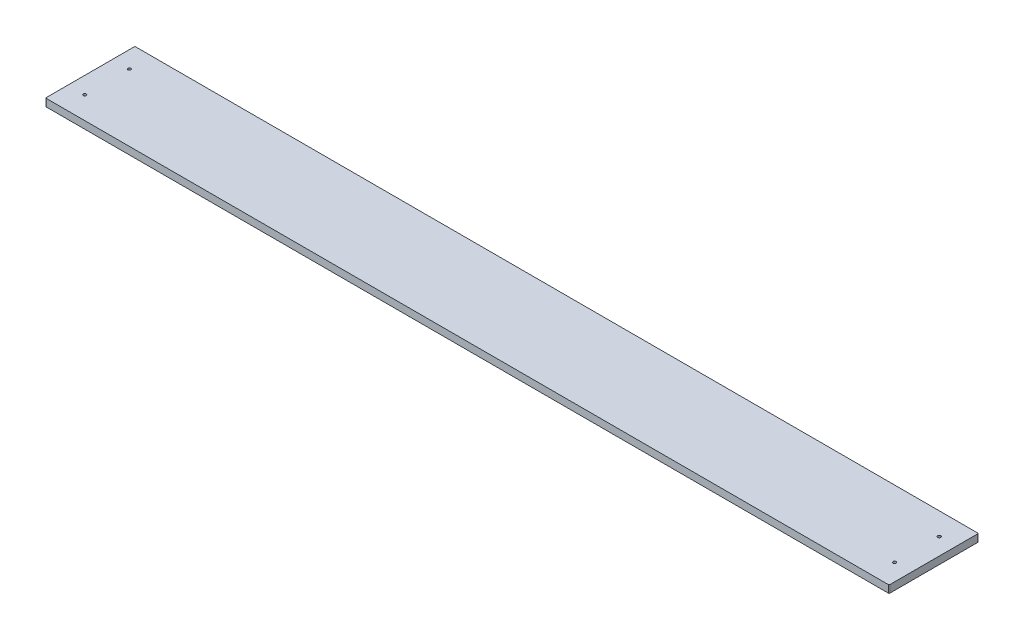
SolidWorks part; units mm, degrees
ref_plane "Front Plane" through (0, 0, 0) normal (0, 0, 1) x (1, 0, 0)
ref_plane "Top Plane" through (0, 0, 0) normal (0, 1, 0) x (1, 0, 0)
ref_plane "Right Plane" through (0, 0, 0) normal (1, 0, 0) x (0, 0, -1)
sketch "Sketch1" plane through (0, 0, 0) normal (0, 1, 0) x (1, 0, 0)
  line L1 (-719.5344, -76.2) -> (719.5344, -76.2)
  line L2 (-719.5344, -76.2) -> (-719.5344, 76.2)
  line L3 (-719.5344, 76.2) -> (719.5344, 76.2)
  line L4 (719.5344, -76.2) -> (719.5344, 76.2)
  line L5 (-719.5344, -76.2) -> (719.5344, 76.2) construction
  line L6 (-719.5344, 76.2) -> (719.5344, -76.2) construction
  point P0 (0, 0)
  dimension "D1" = 1439.0687
  dimension "D2" = 152.4
extrude "Boss-Extrude1" add sketch "Sketch1" along normal blind 12.7
sketch "Sketch2" plane through (0, 12.7, 0) normal (0, 1, 0) x (1, 0, 0)
  line L0 (-610.2712, -25.4) -> (-178.4498, -25.4) construction
  line L1 (-719.5344, -76.2) -> (719.5344, -76.2) construction
  text T0 "OpenAg" font "Circular Std Bold" height in points 190
  point P5 (0, 0)
  point P6 (0, 0)
  dimension "D1" = 50.8
extrude "Cut-Extrude1" [suppressed] cut sketch "Sketch2" against normal through all
sketch "Sketch4" [suppressed] plane through (0, 12.7, 0) normal (0, 1, 0) x (1, 0, 0)
  line L0 (-481.0791, -2.1861) -> (-481.0791, -9.1196) construction
  line L1 (-472.6906, -2.1889) -> (-489.4677, -2.1833) construction
  line L2 (-489.6966, -9.1213) -> (-463.0424, -9.1158) construction
  line L3 (-579.6316, -16.9796) -> (-579.6316, -26.7667) construction
  line L4 (-482.6666, -9.1196) -> (-479.4916, -9.1196)
  line L5 (-482.6666, -9.1196) -> (-482.6666, -2.1861)
  line L6 (-482.6666, -2.1861) -> (-479.4916, -2.1861)
  line L7 (-479.4916, -9.1196) -> (-479.4916, -2.1861)
  line L8 (-482.6666, -9.1196) -> (-479.4916, -2.1861) construction
  line L9 (-482.6666, -2.1861) -> (-479.4916, -9.1196) construction
  line L10 (-388.2394, -3.6437) -> (-388.2394, -13.2985) construction
  line L11 (-525.1122, -25.8875) -> (-525.1122, -16.9456)
  line L12 (-380.7736, -3.6437) -> (-395.7052, -3.6437) construction
  line L13 (-521.9372, -26.0295) -> (-521.9372, -16.7138)
  line L14 (-524.0627, -25.9896) -> (-522.7776, -16.8731) construction
  line L15 (-524.2553, -16.9905) -> (-522.9785, -26.048) construction
  line L16 (-581.2191, -26.7131) -> (-581.2191, -16.9176)
  line L18 (-578.0441, -26.7134) -> (-578.0441, -16.9192)
  line L19 (-580.3862, -26.7446) -> (-578.7706, -16.9569) construction
  line L20 (-580.4927, -16.9565) -> (-578.8769, -26.7447) construction
  line L21 (-389.8269, -3.6437) -> (-386.6519, -3.6437)
  line L22 (-389.8269, -13.2985) -> (-389.8269, -3.6437)
  line L24 (-386.6519, -13.2985) -> (-386.6519, -3.6437)
  line L25 (-388.9668, -13.2985) -> (-387.2862, -3.6437) construction
  line L26 (-389.1926, -3.6437) -> (-387.5119, -13.2985) construction
  line L27 (-389.8269, -13.2985) -> (-386.6519, -13.2985)
  line L28 (-399.2095, -13.2985) -> (-377.2693, -13.2985) construction
  line L29 (-340.3453, -23.877) -> (-340.3453, -14.833)
  line L31 (-337.1703, -23.518) -> (-337.1703, -14.7794)
  line L32 (-339.557, -23.8374) -> (-337.9312, -14.8845) construction
  line L33 (-339.5803, -14.9074) -> (-337.9888, -23.6712) construction
  spline S0 degree 3 poles (-232.3826, -4014.5128) (-589.5598, 58.6836) (-550.0161, -30.9294) (-518.8976, -25.6707) (-517.1471, -25.2295) (-515.5068, -24.6023) (-513.9595, -23.8362) (-512.5345, -22.874) (-511.2004, -21.767) (-509.9827, -20.4984) (-508.8843, -19.1019) (-507.9211, -17.6011) (-507.1154, -15.9982) (-506.4387, -14.3072) (-505.9115, -12.5134) (-505.5254, -10.6262) (-501.1651, 26.981) (-579.9114, 69.01) (3491.1558, -142.4925) knots -3.037277 -3.037277 -3.037277 -3.037277 0.066422 0.130142 0.191626 0.251229 0.309849 0.368247 0.427084 0.487286 0.548172 0.608983 0.669794 0.731835 0.795476 0.861221 0.929106 4.671597 4.671597 4.671597 4.671597 only from (-522.6618, -26.0613) to (-505.2258, -6.5974) construction
  spline S1 degree 3 poles (-3524.9039, -2675.861) (-493.7914, 65.5371) (-547.0805, -9.9244) (-531.7012, -23.3014) (-530.5727, -24.0724) (-529.2816, -24.7561) (-527.8328, -25.3165) (-526.2372, -25.7369) (-493.6012, -30.3889) (-455.2194, 51.5638) (-719.3091, -4020.2296) knots -4.700323 -4.700323 -4.700323 -4.700323 0.099747 0.204713 0.317204 0.437609 0.565438 0.700862 0.845149 8.706276 8.706276 8.706276 8.706276 only from (-533.4297, -21.4824) to (-522.6618, -26.0613) construction
  spline S2 degree 3 poles (-764.9273, -4009.2346) (-479.6751, 45.9502) (-505.35, -19.7883) (-526.1535, -16.8195) (-527.0427, -16.5999) (-527.8929, -16.2994) (-528.6999, -15.9139) (-529.4656, -15.433) (-530.1913, -14.8741) (-530.865, -14.2298) (-531.4869, -13.5163) (-532.0203, -12.7193) (-532.4957, -11.8655) (-532.8599, -10.9307) (-533.1785, -9.9361) (-533.3884, -8.8669) (-536.6586, 15.979) (-468.4943, 46.1951) (-4525.0966, -255.1261) knots -3.830126 -3.830126 -3.830126 -3.830126 0.061922 0.121534 0.180148 0.23681 0.293685 0.350802 0.409399 0.468533 0.528807 0.589992 0.651611 0.715274 0.781491 0.85107 0.923308 5.569004 5.569004 5.569004 5.569004 only from (-524.2599, -16.9906) to (-533.584, -6.5533) construction
  spline S3 degree 3 poles (3481.3499, -156.9784) (-568.7059, 53.7413) (-511.9667, 20.8337) (-515.1906, -8.8868) (-515.4145, -9.9587) (-515.7081, -10.9635) (-516.0837, -11.8943) (-516.537, -12.7549) (-517.0827, -13.5349) (-517.6861, -14.2566) (-518.358, -14.8879) (-519.0671, -15.4521) (-519.8323, -15.9091) (-520.6339, -16.302) (-521.4782, -16.6127) (-522.3715, -16.8169) (-542.8173, -19.8273) (-568.815, 47.0688) (-249.3526, -4006.9857) knots -5.497199 -5.497199 -5.497199 -5.497199 0.078167 0.15112 0.220798 0.287577 0.351331 0.412704 0.473395 0.533298 0.592515 0.649653 0.706482 0.762804 0.820446 0.878294 0.93799 4.771641 4.771641 4.771641 4.771641 only from (-515.0019, -6.5436) to (-524.2599, -16.9906) construction
  spline S4 degree 3 poles (-522.6618, -26.0613) (-522.4202, -26.0514) (-522.1786, -26.0415) (-521.9372, -26.0295) knots 0 0 0 0 0.024766 0.024766 0.024766 0.024766
  spline S5 degree 3 poles (-525.1122, -25.8875) (-524.9203, -25.9119) (-524.1057, -26.0014) (-523.2871, -26.0353) (-522.6618, -26.0613) knots 0.797285 0.797285 0.797285 0.797285 0.845149 1 1 1 1
  spline S6 degree 3 poles (-524.2599, -16.9906) (-524.5443, -16.9794) (-524.8287, -16.9682) (-525.1122, -16.9456) knots 0 0 0 0 0.054403 0.054403 0.054403 0.054403
  spline S7 degree 3 poles (-521.9372, -16.7138) (-522.0788, -16.7468) (-522.5268, -16.8398) (-523.3006, -16.9537) (-523.9361, -16.9782) (-524.2599, -16.9906) knots 0.850466 0.850466 0.850466 0.850466 0.878294 0.93799 1 1 1 1
  spline S8 degree 3 poles (-414.2062, -4021.8002) (-666.0638, 65.3688) (-616.8005, -32.192) (-574.0601, -26.3101) (-571.4242, -25.7324) (-568.9017, -24.9157) (-566.5009, -23.8625) (-564.2141, -22.5885) (-562.0517, -21.0811) (-560.0082, -19.3686) (-558.1491, -17.4324) (-556.4991, -15.2924) (-555.1136, -12.9388) (-553.9475, -10.4002) (-553.0334, -7.6611) (-552.3707, -4.7253) (-545.3969, 43.6041) (-644.8367, 99.7126) (3441.5791, -190.6524) knots -2.707075 -2.707075 -2.707075 -2.707075 0.063988 0.125732 0.185908 0.245066 0.303527 0.361752 0.420628 0.48035 0.540568 0.600591 0.661455 0.723628 0.787936 0.855046 0.925583 4.062887 4.062887 4.062887 4.062887 only from (-579.6316, -26.7667) to (-551.7804, 1.6687) construction
  spline S9 degree 3 poles (-4601.4841, -177.8085) (-512.6365, 98.5074) (-613.7146, 43.1318) (-606.8292, -4.7269) (-606.1504, -7.6599) (-605.2364, -10.3974) (-604.0857, -12.9415) (-602.6972, -15.292) (-601.048, -17.4324) (-599.1891, -19.3691) (-597.1464, -21.0772) (-594.9928, -22.5922) (-592.7092, -23.8592) (-590.3179, -24.9162) (-587.8059, -25.7322) (-585.1811, -26.3101) (-542.608, -32.1917) (-493.4899, 65.3671) (-746.2351, -4021.7021) knots -3.033789 -3.033789 -3.033789 -3.033789 0.074679 0.145306 0.212558 0.276948 0.339098 0.400039 0.460139 0.520434 0.580232 0.63898 0.697279 0.755589 0.814588 0.874599 0.936177 3.700071 3.700071 3.700071 3.700071 only from (-607.4056, 1.6767) to (-579.6316, -26.7667) construction
  spline S10 degree 3 poles (-737.6756, -4012.9491) (-519.6528, 60.3017) (-553.5613, -20.6064) (-582.8719, -16.7316) (-584.4264, -16.3634) (-585.942, -15.8664) (-587.4047, -15.2177) (-588.8158, -14.4108) (-590.1825, -13.4745) (-591.4966, -12.3993) (-592.7125, -11.1671) (-593.786, -9.7742) (-594.6961, -8.2197) (-595.454, -6.5187) (-596.0613, -4.6645) (-596.5063, -2.6637) (-601.9104, 35.7144) (-516.2602, 80.9257) (-4589.3669, -217.9214) knots -2.92755 -2.92755 -2.92755 -2.92755 0.057526 0.113941 0.169804 0.225066 0.281196 0.337514 0.395509 0.454979 0.515539 0.576881 0.639138 0.704237 0.772065 0.843658 0.919218 4.835819 4.835819 4.835819 4.835819 only from (-579.6316, -16.9796) to (-596.9132, 1.7458) construction
  spline S11 degree 3 poles (3430.2012, -219.5229) (-642.9476, 80.9439) (-557.2747, 35.7046) (-562.6798, -2.6636) (-563.1244, -4.6647) (-563.7331, -6.518) (-564.4867, -8.2239) (-565.4148, -9.7665) (-566.4713, -11.1751) (-567.7012, -12.3953) (-569.0144, -13.4741) (-570.3846, -14.4182) (-571.8083, -15.2079) (-573.2737, -15.8751) (-574.798, -16.3585) (-576.3614, -16.7337) (-606.0746, -20.5959) (-640.0689, 60.292) (-437.5272, -4013.4842) knots -3.825587 -3.825587 -3.825587 -3.825587 0.080585 0.155962 0.227381 0.295043 0.359984 0.422286 0.483245 0.543927 0.603252 0.661106 0.717959 0.7736 0.829458 0.885186 0.941845 3.960291 3.960291 3.960291 3.960291 only from (-562.2728, 1.7458) to (-579.6316, -16.9796) construction
  spline S12 degree 3 poles (-579.6316, -26.7667) (-579.1022, -26.7519) (-578.5728, -26.7372) (-578.0441, -26.7134) knots 0 0 0 0 0.035553 0.035553 0.035553 0.035553
  spline S13 degree 3 poles (-581.2191, -26.7131) (-580.6903, -26.7371) (-580.161, -26.7519) (-579.6316, -26.7667) knots 0.964401 0.964401 0.964401 0.964401 1 1 1 1
  spline S14 degree 3 poles (-579.6316, -16.9796) (-580.1613, -16.9681) (-580.691, -16.9565) (-581.2191, -16.9176) knots 0 0 0 0 0.055606 0.055606 0.055606 0.055606
  spline S15 degree 3 poles (-578.0441, -16.9192) (-578.5722, -16.9568) (-579.1019, -16.9682) (-579.6316, -16.9796) knots 0.944531 0.944531 0.944531 0.944531 1 1 1 1
  spline S17 degree 3 poles (-73.8599, -4014.0425) (-406.6219, 61.6391) (-367.8318, -28.7208) (-336.9971, -23.5137) (-335.3976, -23.0478) (-333.9886, -22.4013) (-332.7672, -21.6413) (-331.7249, -20.8128) (-318.0381, -7.0647) (-378.1491, 63.5959) (2858.2152, -2433.4609) knots -7.303392 -7.303392 -7.303392 -7.303392 0.160992 0.309128 0.446329 0.573792 0.693112 0.802897 0.904267 5.484957 5.484957 5.484957 5.484957 only from (-340.6648, -23.8901) to (-330.2054, -18.9414) construction
  spline S18 degree 3 poles (-599.9369, -4005.9241) (-295.968, 54.1888) (-321.2228, -17.735) (-340.8181, -14.7652) (-341.7056, -14.5738) (-342.5427, -14.2925) (-343.3315, -13.9408) (-344.0821, -13.5246) (-344.7624, -13.0073) (-345.4049, -12.44) (-345.9801, -11.7953) (-346.4871, -11.0903) (-346.922, -10.3227) (-347.2723, -9.4932) (-347.5493, -8.6073) (-347.7432, -7.6616) (-350.7729, 14.4207) (-283.0701, 41.6882) (-4339.7637, -252.3928) knots -3.872504 -3.872504 -3.872504 -3.872504 0.067913 0.132756 0.194697 0.254414 0.31393 0.372113 0.430429 0.48927 0.548111 0.607647 0.667517 0.729111 0.792422 0.858052 0.927386 5.368902 5.368902 5.368902 5.368902 only from (-338.9079, -14.9295) to (-347.9169, -5.6165) construction
  spline S19 degree 3 poles (3665.3348, -184.8431) (-389.2625, 43.56) (-327.38, 16.1093) (-330.2096, -7.6408) (-330.4111, -8.577) (-330.6805, -9.4584) (-331.0431, -10.2799) (-331.4536, -11.0558) (-331.9584, -11.7626) (-332.5184, -12.417) (-333.1465, -12.9968) (-333.8228, -13.5114) (-334.5534, -13.9398) (-335.3317, -14.2968) (-336.1602, -14.5716) (-337.036, -14.7645) (-356.1751, -17.7408) (-381.1029, 54.396) (-70.8613, -4005.455) knots -4.747692 -4.747692 -4.747692 -4.747692 0.072513 0.141626 0.207108 0.270995 0.332449 0.393161 0.452797 0.512242 0.57157 0.629805 0.68824 0.746908 0.807169 0.868929 0.932853 4.817567 4.817567 4.817567 4.817567 only from (-330.0511, -5.6165) to (-338.9079, -14.9295) construction
  spline S21 degree 3 poles (-340.3453, -23.877) (-339.804, -23.8541) (-338.7388, -23.7995) (-337.6839, -23.6292) (-337.1703, -23.518) knots 0.026463 0.026463 0.026463 0.026463 0.160992 0.291428 0.291428 0.291428 0.291428
  spline S22 degree 3 poles (-338.9079, -14.9295) (-339.2369, -14.922) (-339.7178, -14.911) (-340.195, -14.8543) (-340.3453, -14.833) knots 0.000311 0.000311 0.000311 0.000311 0.067913 0.099111 0.099111 0.099111 0.099111
  spline S23 degree 3 poles (-337.1703, -14.7794) (-337.4264, -14.8247) (-338.0031, -14.9085) (-338.5855, -14.9221) (-338.9079, -14.9295) knots 0.878947 0.878947 0.878947 0.878947 0.932853 0.99969 0.99969 0.99969 0.99969
  point P6 (-481.0791, -5.6528)
  point P11 (-523.5247, -22.1731)
  point P29 (-579.6316, -22.1731)
  point P46 (-388.2394, -9.1196)
  point P50 (-338.7578, -19.4364)
  dimension "D1" = 3.175
  dimension "D2" = 3.175
extrude "Boss-Extrude2" [suppressed] add sketch "Sketch4" against normal blind 12.7
hole_wizard "#10 Clearance Hole1" positions "Sketch5" profile "Sketch6" hole size "#10" standard "ANSI Inch" end condition through all
sketch "Sketch5" plane through (0, 12.7, 0) normal (0, 1, 0) x (1, 0, 0)
  line L0 (-690.7689, 76.2) -> (-690.7689, -76.2) construction
  line L1 (719.5344, 76.2) -> (-719.5344, 76.2) construction
  line L2 (-719.5344, -76.2) -> (719.5344, -76.2) construction
  line L4 (-719.5344, 76.2) -> (-719.5344, -76.2) construction
  line L5 (-719.5344, 38.1) -> (719.5344, 38.1) construction
  line L6 (719.5344, -76.2) -> (719.5344, 76.2) construction
  line L8 (-719.5344, -38.1) -> (719.5344, -38.1) construction
  line L10 (690.7689, 76.2) -> (690.7689, -76.2) construction
  point P23 (690.7689, 38.1)
  point P25 (690.7689, -38.1)
  point P27 (-690.7689, 38.1)
  point P29 (-690.7689, -38.1)
  point P34 (-690.7689, 38.1)
  point P36 (-690.7689, -38.1)
  point P38 (690.7689, -38.1)
  point P40 (690.7689, 38.1)
  dimension "D1" = 28.7655
  dimension "D2" = 38.1
  dimension "D3" = 38.1
  dimension "D4" = 28.7655
sketch "Sketch6" plane through (690.7689, 12.7, -38.1) normal (1, 0, 0) x (0, 0, 1)
  line L0 (0, 0) -> (0, 12.7)
  line L1 (0, 12.7) -> (2.5527, 12.7)
  line L2 (2.5527, 12.7) -> (2.5527, 0)
  line L5 (2.5527, 0) -> (0, 0)
  line L11 (0, -6.35) -> (0, 107.95) construction
  dimension "Thru Hole Dia." = 5.1054
  dimension "Thru Hole Depth" = 12.7
fillet "Fillet1" radius 1.27 4 edges at (-719.5344, 6.35, 76.2) (-719.5344, 6.35, -76.2) (719.5344, 6.35, 76.2) (719.5344, 6.35, -76.2)
